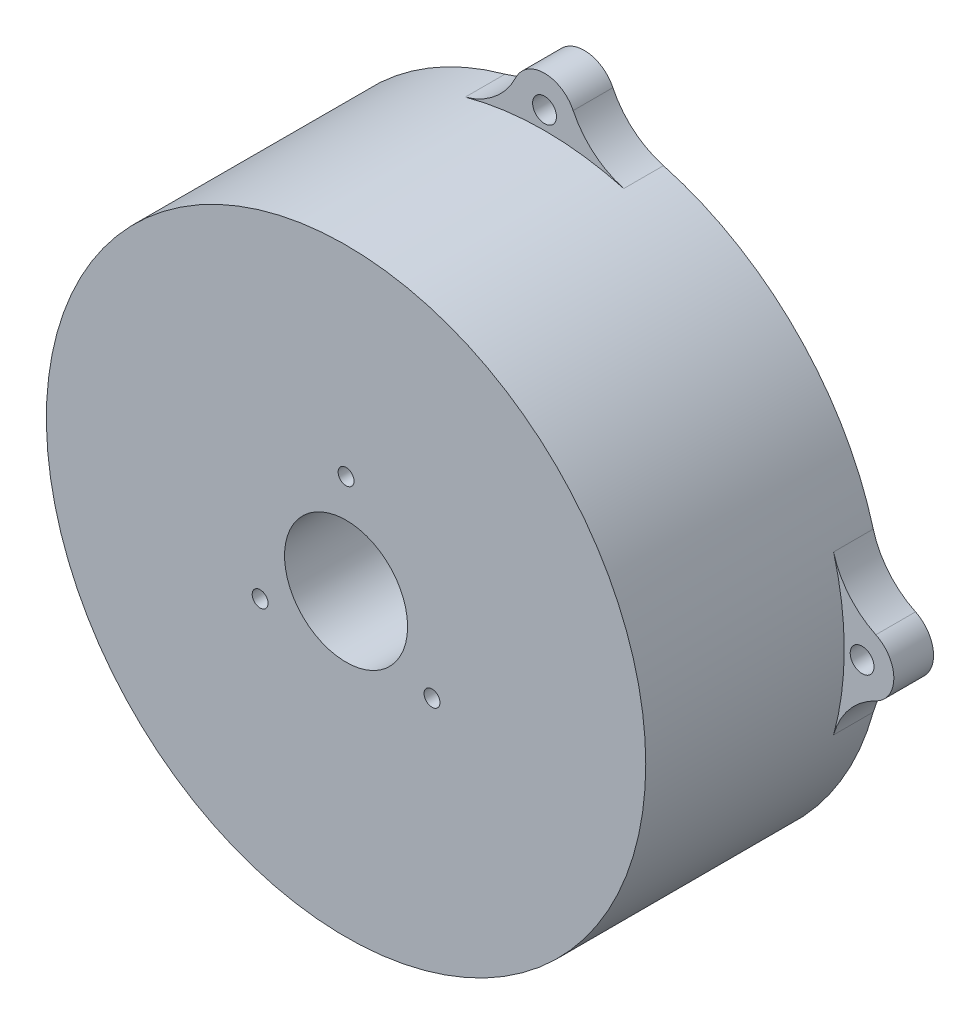
SolidWorks part; units mm, degrees
ref_plane "Front Plane" through (0, 0, 0) normal (0, 0, 1) x (1, 0, 0)
ref_plane "Top Plane" through (0, 0, 0) normal (0, 1, 0) x (1, 0, 0)
ref_plane "Right Plane" through (0, 0, 0) normal (1, 0, 0) x (0, 0, -1)
sketch "Sketch2" plane through (0, 0, 0) normal (0, 0, 1) x (1, 0, 0)
  circle A0 centre (0, 0) radius 37.75
  circle A1 centre (0, 0) radius 7.75
  dimension "D1" = 75.5
  dimension "D2" = 15.5
extrude "Boss-Extrude1" add sketch "Sketch2" along normal blind 30
sketch "Sketch3" plane through (0, 0, 30) normal (0, 0, 1) x (1, 0, 0)
  line L0 (0, 0) -> (0, 28.3756) construction
  circle A0 centre (0, 12.5) radius 1
  circle A1 centre (10.8253, -6.25) radius 1
  circle A2 centre (-10.8253, -6.25) radius 1
  point P12 (0, 0)
  dimension "D1" = 2
  dimension "D2" = 12.5
  dimension "D3" = 3
extrude "Cut-Extrude1" cut sketch "Sketch3" against normal blind 10
sketch "Sketch4" plane through (0, 0, 0) normal (0, 0, -1) x (-1, 0, 0)
  line L0 (0, 0) -> (0, 49.7361) construction
  line L1 (4, 49.1311) -> (4, 34.7702) construction
  line L2 (-4, 48.7816) -> (-4, 33.3405) construction
  line L3 (-4, 40) -> (4, 40) construction
  line L4 (-4, 37.495) -> (0, 37.75)
  line L5 (0, 37.75) -> (4, 37.495)
  line L6 (4, 37.495) -> (4, 40)
  line L7 (-4, 40) -> (-4, 37.495)
  circle A0 centre (0, 40) radius 1.5
  arc A1 (-4, 40) -> (4, 40) centre (0, 40) cw
  circle A2 centre (0, 0) radius 37.75 construction
  dimension "D1" = 3
  dimension "D2" = 4
  dimension "D3" = 4
  dimension "D4" = 40
extrude "Boss-Extrude2" add sketch "Sketch4" against normal blind 5
fillet "Fillet1" radius 10 2 edges at (4, 37.5375, 2.5) (-4, 37.5375, 2.5)
pattern_circular "CirPattern1" count 4 over 360 about axis through (0, 0, 0) along (0, 0, 1) of "Boss-Extrude2", "Fillet1"
